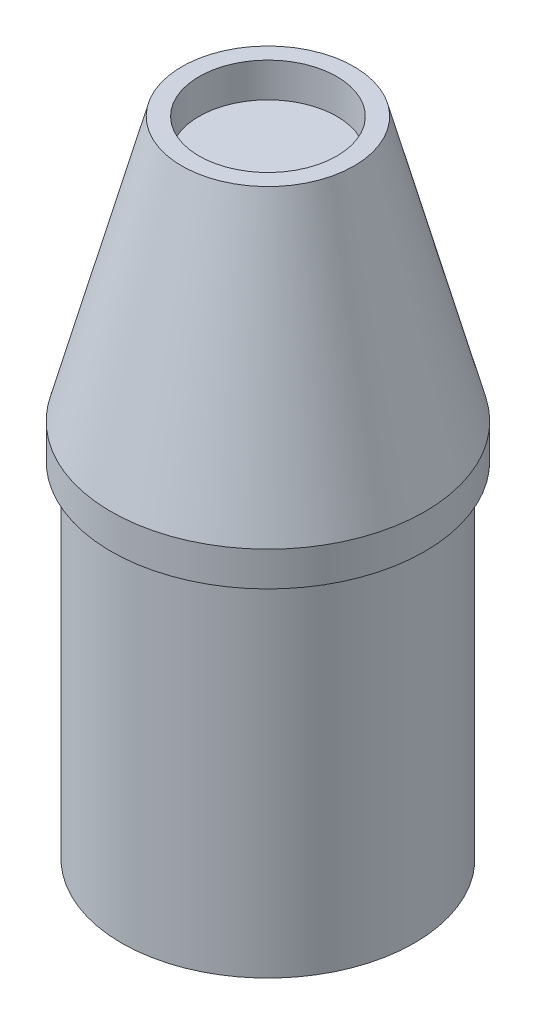
SolidWorks part; units mm, degrees
material "6061 Alloy"
ref_plane "Front Plane" through (0, 0, 0) normal (0, 0, 1) x (1, 0, 0)
ref_plane "Top Plane" through (0, 0, 0) normal (0, 1, 0) x (1, 0, 0)
ref_plane "Right Plane" through (0, 0, 0) normal (1, 0, 0) x (0, 0, -1)
sketch "Sketch1" plane through (0, 0, 0) normal (0, 0, 1) x (1, 0, 0)
  line L0 (0, -13.7747) -> (0, 98.402)
  line L1 (0, 98.402) -> (12.7, 98.402)
  line L2 (12.7, 98.402) -> (12.7, 104.752)
  line L3 (12.7, 104.752) -> (15.875, 104.752)
  line L4 (15.875, 104.752) -> (28.9179, 56.0753)
  line L5 (28.9179, 56.0753) -> (28.9179, 49.7253)
  line L6 (28.9179, 49.7253) -> (26.9875, 49.7253)
  line L7 (26.9875, 49.7253) -> (26.9875, -13.7747)
  line L8 (26.9875, -13.7747) -> (0, -13.7747)
  dimension "D1" = 28.9179
  dimension "D2" = 15
  dimension "D3" = 15.875
  dimension "D5" = 63.5
  dimension "D6" = 6.35
  dimension "D7" = 12.7
  dimension "D8" = 26.9875
revolve "Revolve1" add sketch "Sketch1" angle 360 about L0
